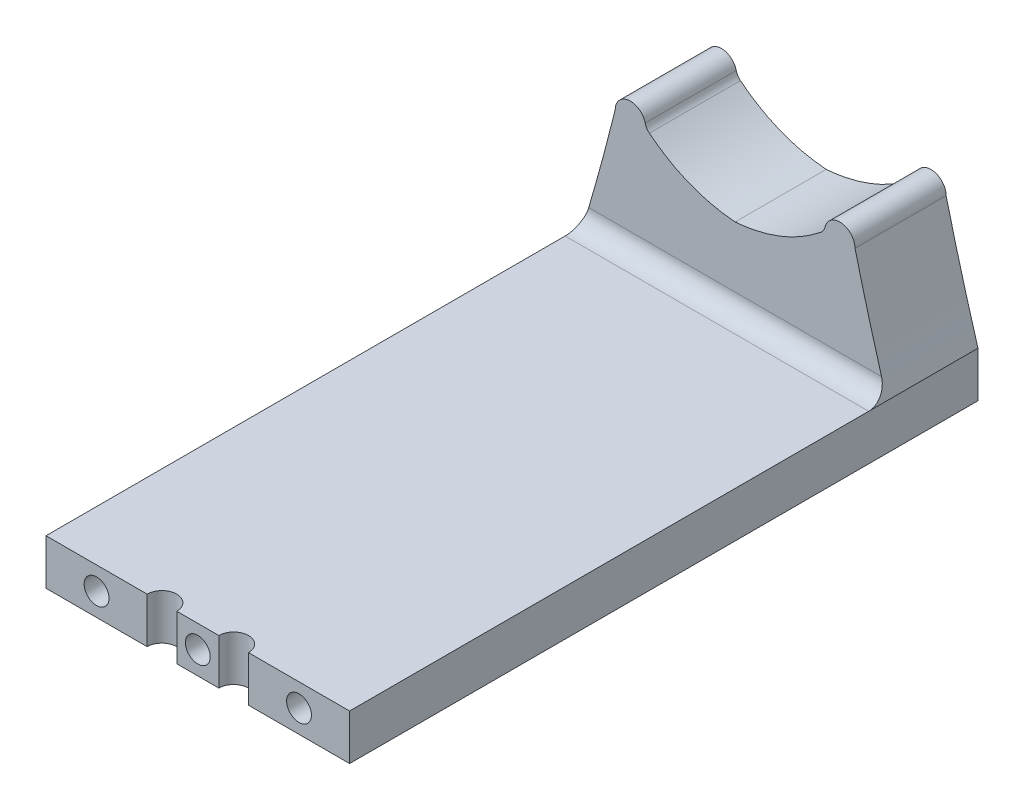
SolidWorks part; units mm, degrees
ref_plane "Front Plane" through (0, 0, 0) normal (0, 0, 1) x (1, 0, 0)
ref_plane "Top Plane" through (0, 0, 0) normal (0, 1, 0) x (1, 0, 0)
ref_plane "Right Plane" through (0, 0, 0) normal (1, 0, 0) x (0, 0, -1)
sketch "Sketch1" plane through (0, 0, 0) normal (0, 0, 1) x (1, 0, 0)
  line L0 (-996.8903, -40.64) -> (49003.1097, -40.64) construction
  line L1 (0, -1000) -> (0, 49000) construction
  line L2 (0, 0) -> (-23.4635, -40.64) construction
  line L3 (0, 0) -> (-40.64, -40.64) construction
  line L4 (-31.75, -62.23) -> (-31.75, -71.755)
  line L5 (-31.75, -71.755) -> (31.75, -71.755)
  line L6 (31.75, -62.23) -> (31.75, -71.755)
  line L7 (-957.5735, -46.99) -> (49042.4265, -46.99) construction
  circle A0 centre (0, 0) radius 40.64 construction
  arc A1 (-18.7325, -37.9449) -> (-25.0825, -37.9449) centre (-21.9075, -37.9449) ccw
  arc A2 (18.7325, -37.9449) -> (25.0825, -37.9449) centre (21.9075, -37.9449) cw
  spline S0 degree 2 poles (-18.7325, -37.9449) (-10.6333, -44.8669) (0, -45.72) knots 0 0 0 1 1 1
  spline S1 degree 2 poles (-25.0825, -37.9449) (-28.1202, -50.167) (-31.75, -62.23) knots 0 0 0 1 1 1
  spline S2 degree 2 poles (25.0825, -37.9449) (28.1202, -50.167) (31.75, -62.23) knots 0 0 0 1 1 1
  spline S3 degree 2 poles (18.7325, -37.9449) (10.6333, -44.8669) (0, -45.72) knots 0 0 0 1 1 1
  point P13 (0, -71.755)
  dimension "D1" = 81.28
  dimension "D3" = 6.35
  dimension "D5" = 5.08
  dimension "D2" = 30
  dimension "D4" = 45
  dimension "D6" = 31.75
  dimension "D7" = 9.525
  dimension "D8" = 21.59
  dimension "D9" = 6.35
extrude "Boss-Extrude1" add sketch "Sketch1" along normal mid plane 19.05
sketch "Sketch2" plane through (0, 0, 0) normal (0, 0, 1) x (1, 0, 0)
  line L1 (-31.75, -62.23) -> (31.75, -62.23)
  line L2 (-31.75, -62.23) -> (-31.75, -71.755)
  line L3 (-31.75, -71.755) -> (31.75, -71.755)
  line L4 (31.75, -62.23) -> (31.75, -71.755)
extrude "Boss-Extrude2" add sketch "Sketch2" along normal blind 121.92
fillet "Fillet2" radius 2.54 2 edges at (18.7325, -37.9449, 0) (-18.7325, -37.9449, 0)
sketch "Sketch3" plane through (0, -62.23, 0) normal (0, 1, 0) x (1, 0, 0)
  line L0 (31.75, -121.92) -> (-31.75, -121.92) construction
  line L1 (0, -9.525) -> (0, 9.525) construction
  circle A0 centre (7.5, -121.92) radius 3.1
  circle A1 centre (-7.5, -121.92) radius 3.1
  dimension "D1" = 6.2
  dimension "D2" = 7.5
extrude "Cut-Extrude1" cut sketch "Sketch3" against normal through all
ref_plane "wheel_tangent_plane" through (0, -40.64, 0) normal (0, 1, 0) x (1, 0, 0)
ref_plane "offset_0.1in_aka_poly_top" through (0, -43.18, 0) normal (0, 1, 0) x (1, 0, 0)
sketch "Sketch4" plane through (0, 0, 121.92) normal (0, 0, 1) x (1, 0, 0)
  circle A0 centre (-21.175, -66.9925) radius 2.6
  circle A1 centre (0, -66.9925) radius 2.6
  circle A2 centre (21.175, -66.9925) radius 2.6
  point P6 (-21.175, -66.9925)
  dimension "D1" = 5.2
  dimension "D2" = 5.2
  dimension "D3" = 5.2
extrude "Cut-Extrude2" cut sketch "Sketch4" against normal blind 9.525
fillet "Fillet3" radius 3.81 1 edges at (0, -62.23, 9.525) type face fillet first side face at (2.7343, -43.5854, 9.525) second side face at (0, -62.23, 93.0462)
